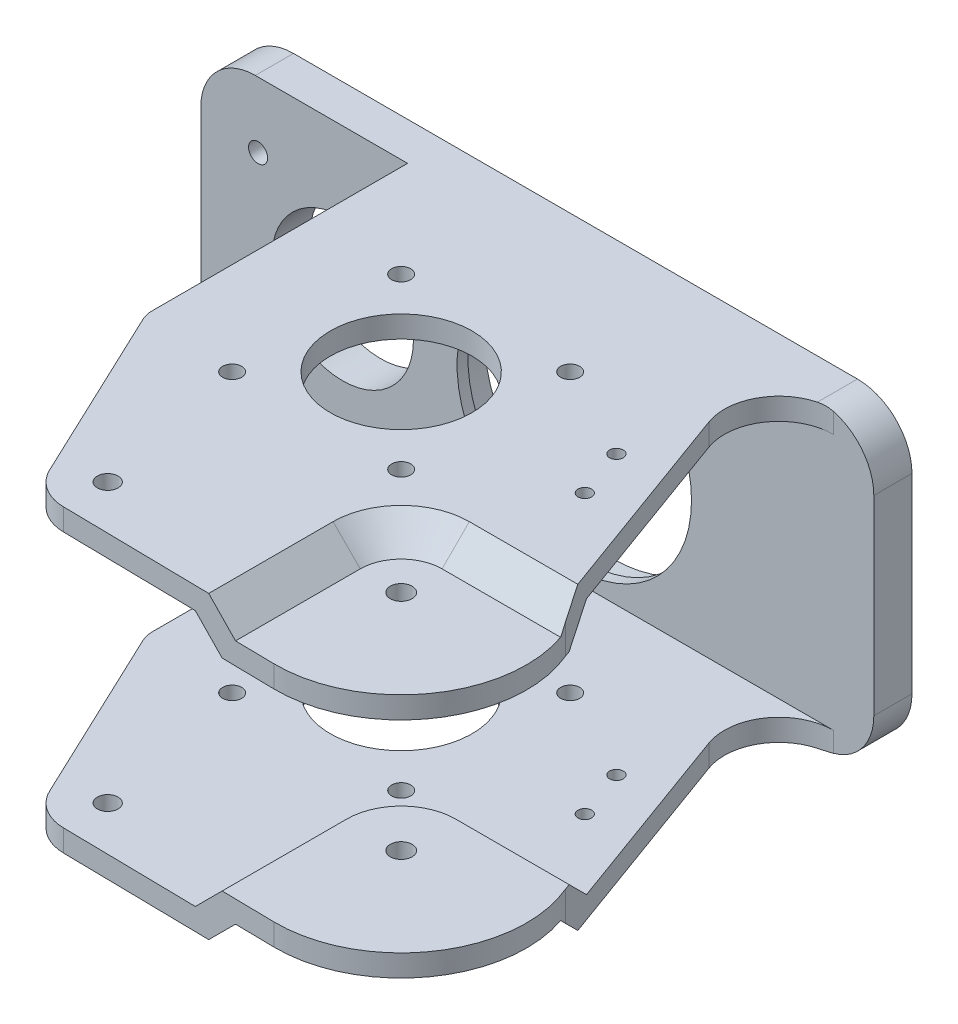
SolidWorks part; units mm, degrees
ref_plane "前视基准面" through (0, 0, 0) normal (0, 0, 1) x (1, 0, 0)
ref_plane "上视基准面" through (0, 0, 0) normal (0, 1, 0) x (1, 0, 0)
ref_plane "右视基准面" through (0, 0, 0) normal (1, 0, 0) x (0, 0, -1)
sketch "草图2" plane through (0, 0, 0) normal (0, 0, 1) x (1, 0, 0)
  line B0 (-68.5, -27.5) -> (54.9402, -27.5)
  line B1 (-68.5, 27.5) -> (54.9402, 27.5)
  line B2 (54.9402, 27.5) -> (54.9402, -27.5)
  line B3 (-68.5, -27.5) -> (-68.5, 27.5)
  circle B4 centre (0, 0) radius 23.5
  circle B5 centre (-42.5, 0) radius 13
  circle B6 centre (-27, 15.5) radius 1.75
  circle B7 centre (-27, -15.5) radius 1.75
  circle B8 centre (-58, -15.5) radius 1.75
  circle B9 centre (-58, 15.5) radius 1.75
sketch_block_instance "块1-1"
sketch_block "块1"
extrude "凸台-拉伸1" add sketch "草图2" along normal blind 7
sketch "草图3" plane through (0, -27.5, 0) normal (0, -1, 0) x (1, 0, 0)
  line L0 (-68.5, 0) -> (54.9402, 0) construction
  line B0 (-42.5, 7) -> (-42.5, 0)
  line B1 (54.9402, 7) -> (54.9402, 0)
  line B2 (-68.5, 7) -> (-68.5, 0)
  line B3 (-27, 7) -> (-27, 0)
  line B4 (-58, 7) -> (-58, 0)
  line B5 (23.5, 5) -> (23.5, 0)
  line B6 (-23.5, 5) -> (-23.5, 0)
  line B7 (-23.5, 5) -> (23.5, 5)
  line B8 (-68.5, 0) -> (54.9402, 0)
  line B9 (-68.5, 7) -> (54.9402, 7)
  line B10 (38.1287, 20.4202) -> (53.5531, 62.7984)
  line B11 (-30.5763, 53.7763) -> (-30.5763, 7)
  line B12 (37.0402, 93.0923) -> (-0.2258, 101.5692)
  line B13 (-9.14, 97.3773) -> (-30.0386, 56.0319)
  arc B14 (38.1287, 20.4202) -> (47.5256, 7) centre (47.5256, 17) ccw
  circle B15 centre (34.7267, 34) radius 1.25
  circle B16 centre (38.0443, 43.115) radius 1.25
  circle B17 centre (32, 70.7505) radius 2
  arc B18 (53.5531, 62.7984) -> (37.0402, 93.0923) centre (31.9402, 70.6649) ccw
  arc B19 (-0.2258, 101.5692) -> (-9.14, 97.3773) centre (-2.0002, 93.7684) ccw
  arc B20 (-30.0386, 56.0319) -> (-30.5763, 53.7763) centre (-25.5763, 53.7763) ccw
  circle B21 centre (-2.4642, 94.7551) radius 1.9
  circle B22 centre (1.948, 40.6985) radius 13
  circle B23 centre (-13.552, 56.1985) radius 1.75
  circle B24 centre (17.448, 56.1985) radius 1.75
  circle B25 centre (17.448, 25.1985) radius 1.75
  circle B26 centre (-13.552, 25.1985) radius 1.75
sketch_block_instance "块2-1"
sketch_block "块2"
sketch "草图5" plane through (0, 27.5, 0) normal (0, 1, 0) x (1, 0, 0)
  line L3 (54.9402, -7) -> (-68.5, -7) construction
  point P2 (0.001, -0.001)
  point P76 (0.001, 0)
  line B0 (-30.5763, -7) -> (47.5256, -7)
  line B1 (38.1287, -20.4202) -> (53.2072, -61.848)
  line B2 (-30.5763, -53.8454) -> (-30.5763, -7)
  line B3 (-30.0962, -55.9832) -> (-14.6989, -88.536)
  line B4 (-7.5962, -93.1143) -> (31.6288, -93.7475)
  arc B5 (38.1287, -20.4202) -> (47.5256, -7) centre (47.5256, -17) cw
  circle B6 centre (34.7267, -34) radius 1.25
  circle B7 centre (38.0443, -43.115) radius 1.25
  circle B8 centre (32, -70.7505) radius 2
  circle B9 centre (1.948, -40.6985) radius 13
  circle B10 centre (-13.552, -56.1985) radius 1.75
  circle B11 centre (17.448, -56.1985) radius 1.75
  circle B12 centre (17.448, -25.1985) radius 1.75
  circle B13 centre (-13.552, -25.1985) radius 1.75
  circle B14 centre (-7.4671, -85.1154) radius 1.9
  arc B15 (-30.0962, -55.9832) -> (-30.5763, -53.8454) centre (-25.5763, -53.8454) cw
  arc B16 (-7.5962, -93.1143) -> (-14.6989, -88.536) centre (-7.4671, -85.1154) cw
  arc B17 (53.2072, -61.848) -> (31.6288, -93.7475) centre (32, -70.7505) cw
sketch_block_instance "块5-2"
sketch_block "块5"
extrude "凸台-拉伸3" add sketch "草图5" against normal blind 4
sketch "草图6" plane through (0, 0, 7) normal (0, 0, 1) x (1, 0, 0)
  circle A0 centre (0, 0) radius 21.5
  circle A2 centre (0, 0) radius 23.5 construction
  circle A3 centre (0, 0) radius 23.5
  dimension "D1" = 2
extrude "凸台-拉伸4" add sketch "草图6" against normal blind 2
mirror "镜向1" about plane through (0, 0, 0) normal (0, 1, 0) of "凸台-拉伸3"
fillet "圆角1" radius 10 4 edges at (54.9402, 27.5, 3.5) (54.9402, -27.5, 3.5) (-68.5, 27.5, 3.5) (-68.5, -27.5, 3.5)
sketch "草图7" plane through (0, 0, 0) normal (0, 0, 1) x (1, 0, 0)
  circle A0 centre (-58, 15.5) radius 3.25
  circle A1 centre (-27, 15.5) radius 3.25
  circle A2 centre (-27, -15.5) radius 3.25
  circle A3 centre (-58, -15.5) radius 3.25
  dimension "D1" = 6.5
extrude "切除-拉伸4" cut sketch "草图7" along normal blind 4
sketch "草图18" plane through (0, -23.5, 0) normal (0, 1, 0) x (1, 0, 0)
  line L0 (32, -55.7505) -> (50.9879, -55.7505)
  line L1 (17, -70.7505) -> (17, -93.5114)
  line L2 (53.2072, -61.848) -> (38.1287, -20.4202) construction
  line L3 (-7.5962, -93.1143) -> (31.6288, -93.7475) construction
  line L4 (53.2072, -61.848) -> (50.9879, -55.7505)
  line L5 (17, -93.5114) -> (31.6288, -93.7475)
  arc A0 (32, -55.7505) -> (17, -70.7505) centre (32, -70.7505) ccw
  arc A1 (31.6288, -93.7475) -> (53.2072, -61.848) centre (32, -70.7505) ccw construction
  arc A2 (31.6288, -93.7475) -> (53.2072, -61.848) centre (32, -70.7505) ccw
  circle A3 centre (32, -70.7505) radius 2 construction
  circle A4 centre (32, -70.7505) radius 2
  dimension "D1" = 30
extrude "凸台-拉伸7" add sketch "草图18" along normal blind 5
sketch "草图9" plane through (0, -27.5, 0) normal (0, -1, 0) x (1, 0, 0)
  line L0 (19.5, 70.7505) -> (19.5, 93.5517)
  line L1 (32, 58.2505) -> (51.8978, 58.2505)
  line L6 (-7.5962, 93.1143) -> (31.6288, 93.7475) construction
  line L7 (53.2072, 61.848) -> (38.1287, 20.4202) construction
  line L8 (19.5, 93.5517) -> (31.6288, 93.7475)
  line L9 (53.2072, 61.848) -> (51.8978, 58.2505)
  arc A0 (19.5, 70.7505) -> (32, 58.2505) centre (32, 70.7505) ccw
  arc A3 (53.2072, 61.848) -> (31.6288, 93.7475) centre (32, 70.7505) ccw construction
  arc A4 (53.2072, 61.848) -> (31.6288, 93.7475) centre (32, 70.7505) ccw
  dimension "D1" = 25
extrude "切除-拉伸5" cut sketch "草图9" against normal blind 5
chamfer "倒角8" distance 5 angle 45 6 edges at (41.9489, -22.5, 58.2505) (23.1612, -22.5, 61.9117) (19.5, -22.5, 82.1511) (41.4939, -18.5, 55.7505) (21.3934, -18.5, 60.1439) (17, -18.5, 82.131)
mirror "镜向2" about plane through (0, 0, 0) normal (0, 1, 0) of "凸台-拉伸7", "倒角8", "切除-拉伸5"
